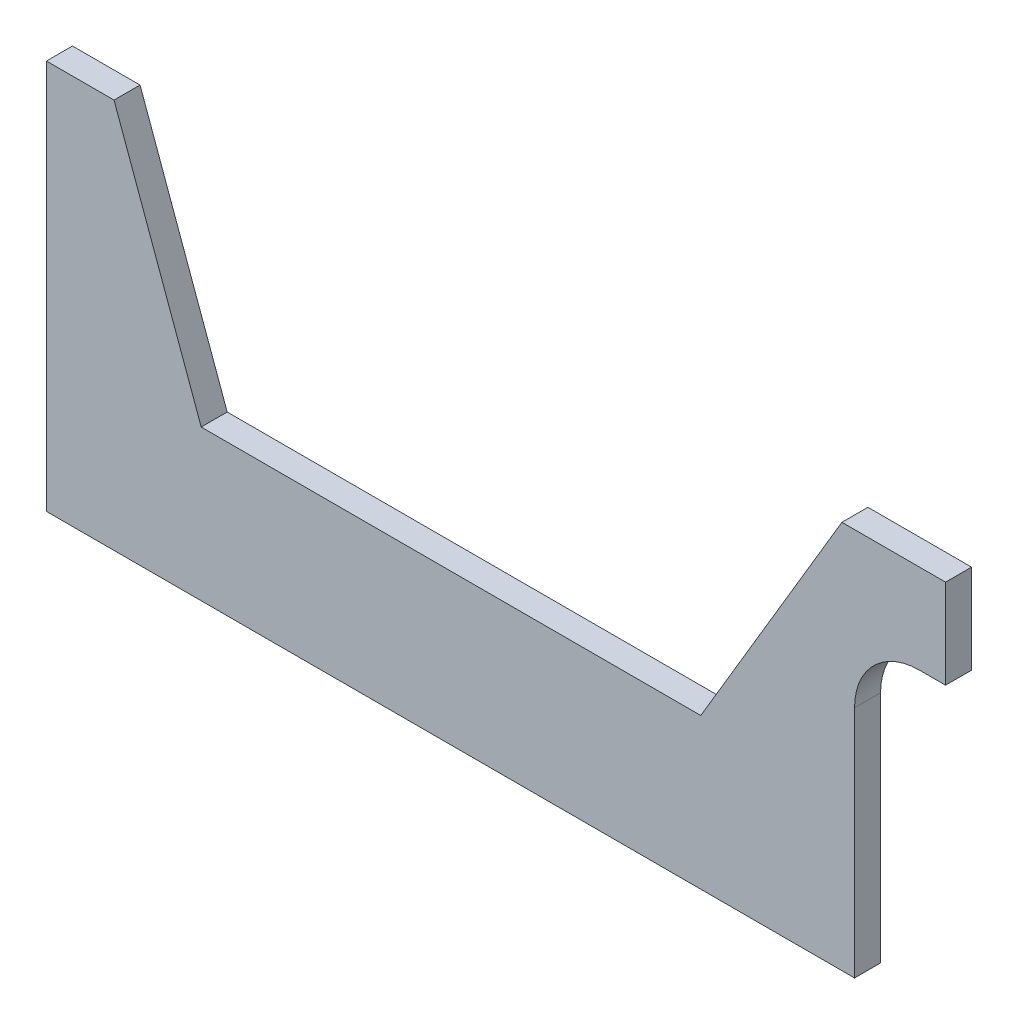
SolidWorks part; units mm, degrees
ref_plane "Front Plane" through (0, 0, 0) normal (0, 0, 1) x (1, 0, 0)
ref_plane "Top Plane" through (0, 0, 0) normal (0, 1, 0) x (1, 0, 0)
ref_plane "Right Plane" through (0, 0, 0) normal (1, 0, 0) x (0, 0, -1)
sketch "Sketch1" plane through (0, 0, 0) normal (0, 0, 1) x (1, 0, 0)
  line L2 (-60.75, -30) -> (-60.75, 30)
  line L11 (63.5497, 16) -> (77.5497, 16)
  line L18 (63.5497, -30) -> (63.5497, 16)
  line L21 (77.5497, 29.7321) -> (77.5497, 16)
  line L23 (-60.75, 30) -> (-50.3529, 30)
  line L24 (-50.3529, 30) -> (-36.9454, -6.8552)
  line L25 (-36.9454, -6.8552) -> (39.8971, -6.8552)
  line L26 (39.8971, -6.8552) -> (61.6068, 29.7321)
  line L27 (61.6068, 29.7321) -> (77.5497, 29.7321)
  line L29 (-60.75, -30) -> (63.5497, -30)
  point P5 (57.5068, 27.2401)
  point P8 (-50.3529, 27.5)
  point P12 (-37.1456, -8.8049)
  point P13 (-60.75, 0)
  point P15 (39.8971, -9.3552)
  dimension "D1" = 138.3
  dimension "D2" = 14
  dimension "D3" = 46
  dimension "D4" = 60
extrude "Boss-Extrude1" add sketch "Sketch1" along normal mid plane 4
fillet "Fillet1" radius 10 1 edges at (63.5497, 16, 0)
equation "\"wall_thick_ness\"=4"
equation "\"D1@Boss-Extrude1\"=\"wall_thick_ness\""
equation "\"back_boost\"=7"
equation "\"D1@Sketch1\"=\"back_boost\"+131.30mm"
